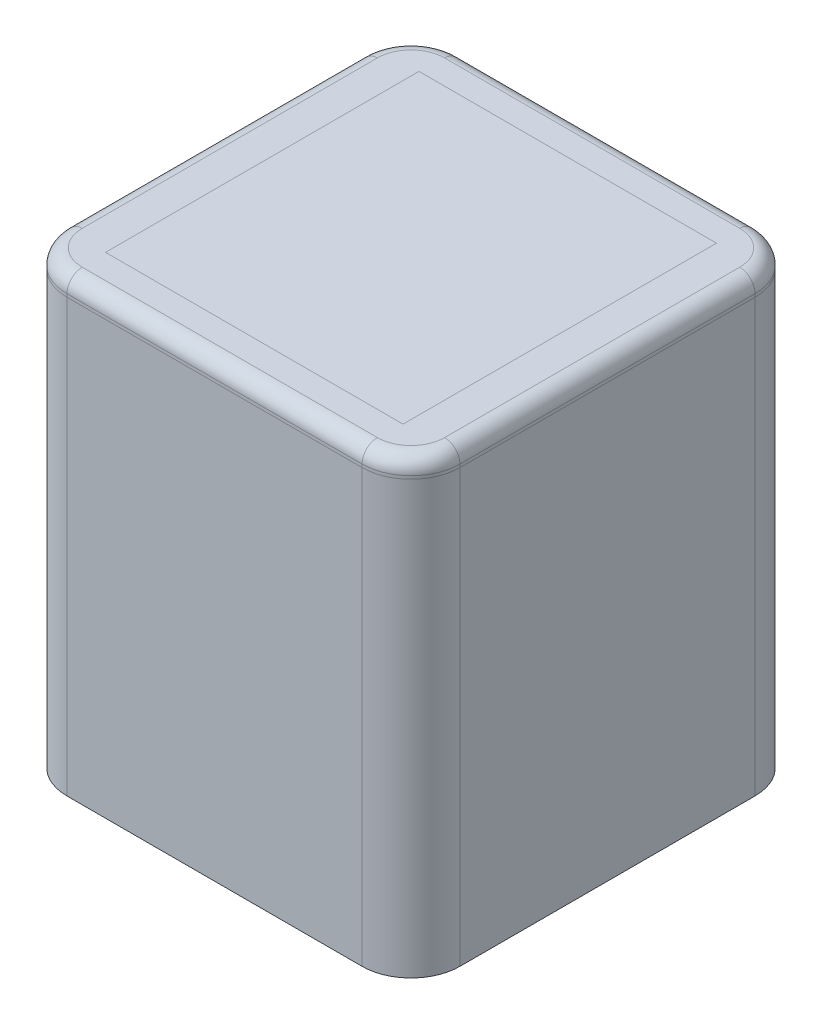
SolidWorks part; units mm, degrees
ref_plane "Front Plane" through (0, 0, 0) normal (0, 0, 1) x (1, 0, 0)
ref_plane "Top Plane" through (0, 0, 0) normal (0, 1, 0) x (1, 0, 0)
ref_plane "Right Plane" through (0, 0, 0) normal (1, 0, 0) x (0, 0, -1)
sketch "Sketch1" plane through (0, 0, 0) normal (0, 1, 0) x (1, 0, 0)
  line L0 (0, 12.85) -> (0, 0) construction
  line L1 (-12.85, -12.85) -> (12.85, -12.85)
  line L2 (-12.85, -12.85) -> (-12.85, 12.85)
  line L3 (-12.85, 12.85) -> (12.85, 12.85)
  line L4 (12.85, -12.85) -> (12.85, 12.85)
  line L5 (0, 0) -> (-12.85, 0) construction
  line L6 (-9.7286, -10.25) -> (-9.7286, 10.25)
  line L7 (9.7286, 10.25) -> (-9.7286, 10.25)
  line L8 (9.7286, -10.25) -> (9.7286, 10.25)
  line L9 (9.7286, -10.25) -> (-9.7286, -10.25)
  point P9 (0, 12.85)
  point P12 (-9.7286, 0)
  point P15 (0, 10.25)
  point P17 (9.7286, 0)
  point P18 (0, -10.25)
  dimension "D1" = 25.7
  dimension "D2" = 20.5
extrude "Boss-Extrude1" add sketch "Sketch1" along normal blind 28.25 contours L2 L3 L4 L1 | L8 L7 L6 L9
extrude "Boss-Extrude4" add sketch "Sketch1<5>" along normal blind 22.86 contours L9 L8 L7 L6 region at (0, 0, 0)
sketch "Sketch1<5>" plane through (0, 0, 0) normal (0, 1, 0) x (1, 0, 0) same geometry as "Sketch1"
extrude "Boss-Extrude2" add sketch "Sketch1<3>" along normal blind 1.2 from surface separate body contours L9 L6 L7 L8 starting at face at (0, 28.25, 0)
sketch "Sketch1<3>" plane through (0, 0, 0) normal (0, 1, 0) x (1, 0, 0) same geometry as "Sketch1"
extrude "Boss-Extrude3" add sketch "Sketch1<4>" along normal up to surface (29.45 mm away) from surface separate body contours L1 L4 L3 L2 | L9 L6 L7 L8 up to face at (0, 29.45, 0) starting at face at (0, 28.25, 0)
sketch "Sketch1<4>" plane through (0, 0, 0) normal (0, 1, 0) x (1, 0, 0) same geometry as "Sketch1"
fillet "Fillet1" radius 3.2 4 edges at (-12.85, 14.125, -12.85) (12.85, 14.125, -12.85) (12.85, 14.125, 12.85) (-12.85, 14.125, 12.85)
fillet "Fillet2" radius 3.2 4 edges at (-12.85, 28.85, -12.85) (12.85, 28.85, -12.85) (12.85, 28.85, 12.85) (-12.85, 28.85, 12.85)
fillet "Fillet3" radius 1 8 edges at (11.9127, 29.45, 11.9127) (0, 29.45, 12.85) (-11.9127, 29.45, 11.9127) (-12.85, 29.45, 0) (-11.9127, 29.45, -11.9127) (0, 29.45, -12.85) (11.9127, 29.45, -11.9127) (12.85, 29.45, 0)
